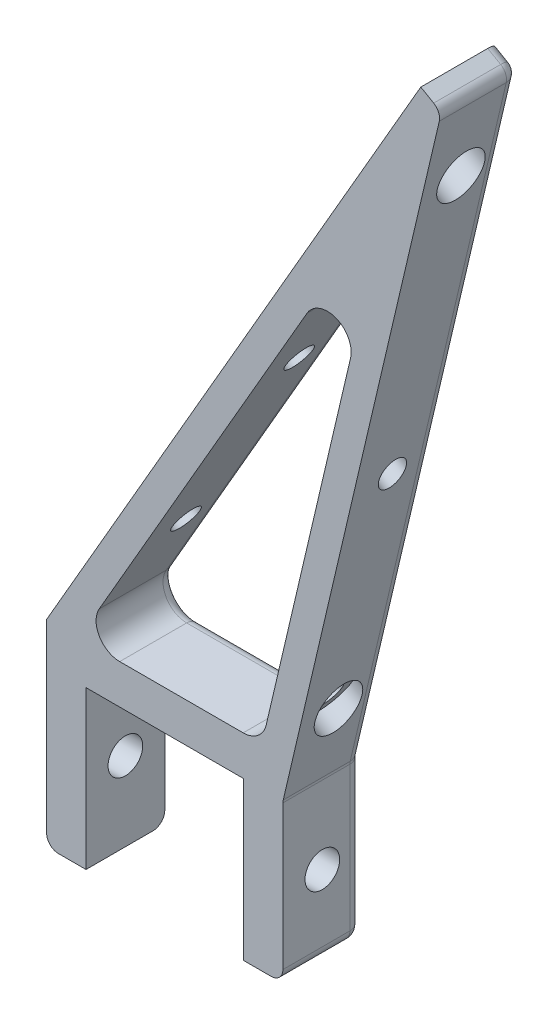
SolidWorks part; units mm, degrees
material "ABS"
ref_plane "Front Plane" through (0, 0, 0) normal (0, 0, 1) x (1, 0, 0)
ref_plane "Top Plane" through (0, 0, 0) normal (0, 1, 0) x (1, 0, 0)
ref_plane "Right Plane" through (0, 0, 0) normal (1, 0, 0) x (0, 0, -1)
sketch "Sketch1" plane through (0, 0, 0) normal (0, 0, 1) x (1, 0, 0)
  line L0 (-10, -20) -> (-10, 0)
  line L1 (-10, 0) -> (10, 0)
  line L2 (10, 0) -> (10, -20)
  line L3 (10, -20) -> (15, -20)
  line L4 (15, -20) -> (15, 0)
  line L5 (15, 0) -> (35.1015, 85.7704)
  line L6 (32.5, 87.2724) -> (-15, 5)
  line L7 (-15, 5) -> (-15, -20)
  line L8 (-15, -20) -> (-10, -20)
  line L9 (32.5, 87.2724) -> (35.1015, 85.7704)
  dimension "D1" = 5
  dimension "D2" = 20
  dimension "D3" = 20
  dimension "D4" = 166.81
  dimension "D5" = 150
  dimension "D6" = 20
  dimension "D7" = 25
  dimension "D8" = 95
extrude "Boss-Extrude1" add sketch "Sketch1" along normal blind 10
sketch "Sketch2" plane through (0, 0, 10) normal (0, 0, 1) x (1, 0, 0)
  line L0 (-10.9175, 5) -> (28.2148, 72.7791)
  line L1 (28.2148, 72.7791) -> (12.3298, 5)
  line L2 (12.3298, 5) -> (-10.9175, 5)
  line L3 (-10, 0) -> (10, 0) construction
  line L5 (15, 0) -> (35.1015, 85.7704) construction
  line L6 (32.5, 87.2724) -> (-15, 5) construction
  dimension "D1" = 5
  dimension "D2" = 3.7406
  dimension "D3" = 3.5356
extrude "Cut-Extrude1" cut sketch "Sketch2" against normal through all
fillet "Fillet1" radius 3 3 edges at (-10.9175, 5, 5) (12.3298, 5, 5) (28.2148, 72.7791, 5)
fillet "Fillet2" radius 1.5 16 edges at (35.1015, 85.7704, 5) (15, 0, 5) (15, -20, 5) (-15, -20, 5) (-8.3194, 6.5, 0) (4.8718, 32.3478, 0) (21.7651, 56.485, 0) (18.2272, 30.1633, 0) (11.8153, 5.6491, 0) (33.8007, 86.5214, 0) (25.0507, 42.8852, 0) (15, -10, 0) (12.5, -20, 0) (-15, -7.5, 0) (-12.5, -20, 0) (2.1151, 5, 0)
sketch "Sketch3" plane through (-15, 0, 0) normal (-1, 0, 0) x (0, 0, 1)
  line L0 (0, 5) -> (0, -18.5) construction
  line L1 (10, -20) -> (1.5, -20) construction
  circle A0 centre (5, -10) radius 2.2
  dimension "D1" = 5
  dimension "D2" = 10
  dimension "D3" = 4.4
extrude "Cut-Extrude2" cut sketch "Sketch3" against normal through all
sketch "Sketch4" plane through (-13.4151, 7.7452, 0) normal (-0.866, 0.5, 0) x (0, 0, 1)
  line L0 (10, 23.3264) -> (0, 23.3264) construction
  line L1 (10, 91.8301) -> (10, -3.1699) construction
  line L2 (0, 90.3301) -> (0, -0.1699) construction
  line L3 (5, 16.0989) -> (5, 23.3264) construction
  line L4 (10, 91.8301) -> (1.5, 91.8301) construction
  circle A0 centre (5, 81.3301) radius 1.75
  circle A1 centre (5, 44.8301) radius 1.75
  circle A2 centre (5, 16.0989) radius 1.75
  dimension "D1" = 3.5
  dimension "D2" = 10.5
  dimension "D3" = 36.5
  dimension "D4" = 28.7312
extrude "Cut-Extrude3" cut sketch "Sketch4" against normal through all
sketch "Sketch5" plane through (-13.4805, 7.6318, 0) normal (0.866, -0.5, 0) x (0, 0, -1)
  circle A0 centre (-5, 81.4611) radius 3
  dimension "D1" = 6
extrude "Cut-Extrude4" cut sketch "Sketch5" along normal through all from offset 3
sketch "Sketch6" plane through (-13.4151, 7.7452, 0) normal (-0.866, 0.5, 0) x (0, 0, 1)
  circle A0 centre (5, 16.0989) radius 3
  dimension "D1" = 6
extrude "Cut-Extrude5" cut sketch "Sketch6" against normal through all from offset 24.38 offset against normal yes
